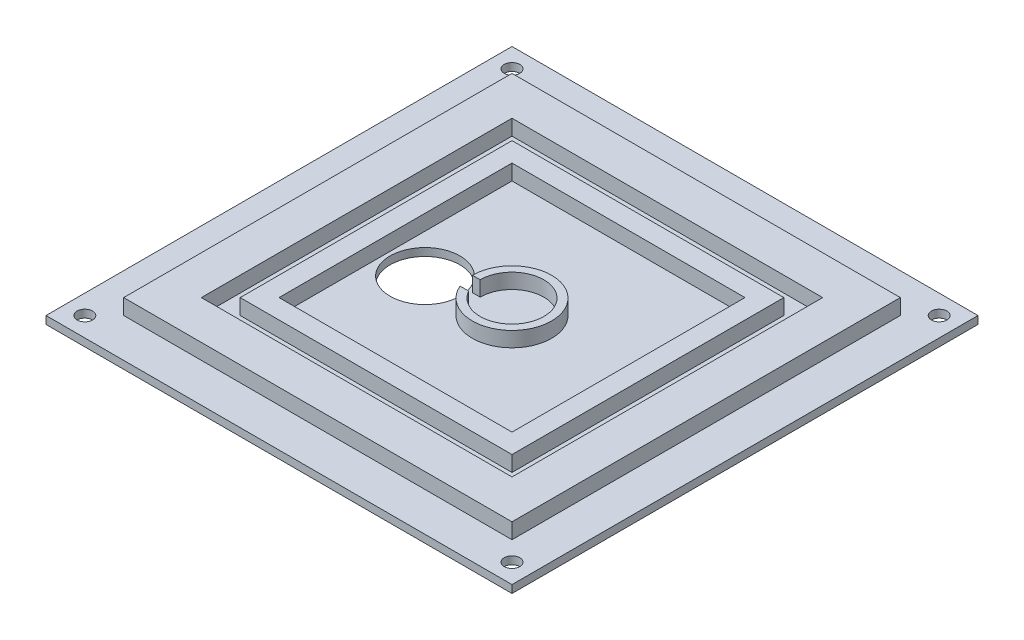
SolidWorks part; units mm, degrees
ref_plane "Front Plane" through (0, 0, 0) normal (0, 0, 1) x (1, 0, 0)
ref_plane "Top Plane" through (0, 0, 0) normal (0, 1, 0) x (1, 0, 0)
ref_plane "Right Plane" through (0, 0, 0) normal (1, 0, 0) x (0, 0, -1)
sketch "Sketch1" plane through (0, 0, 0) normal (0, 1, 0) x (1, 0, 0)
  line L1 (-76.2, 76.2) -> (76.2, 76.2)
  line L2 (-76.2, 76.2) -> (-76.2, -76.2)
  line L3 (-76.2, -76.2) -> (76.2, -76.2)
  line L4 (76.2, 76.2) -> (76.2, -76.2)
  line L5 (-76.2, 76.2) -> (76.2, -76.2) construction
  line L6 (-76.2, -76.2) -> (76.2, 76.2) construction
  point P0 (0, 0)
  dimension "D1" = 152.4
  dimension "D2" = 152.4
extrude "Boss-Extrude1" add sketch "Sketch1" against normal blind 2.54
sketch "Sketch2" plane through (0, 0, 0) normal (0, 1, 0) x (1, 0, 0)
  line L1 (63.5, -63.5) -> (-63.5, -63.5)
  line L2 (63.5, -63.5) -> (63.5, 63.5)
  line L3 (63.5, 63.5) -> (-63.5, 63.5)
  line L4 (-63.5, -63.5) -> (-63.5, 63.5)
  line L5 (63.5, -63.5) -> (-63.5, 63.5) construction
  line L6 (63.5, 63.5) -> (-63.5, -63.5) construction
  line L7 (-57.15, 57.15) -> (57.15, 57.15)
  line L8 (-57.15, 57.15) -> (-57.15, -57.15)
  line L9 (-57.15, -57.15) -> (57.15, -57.15)
  line L10 (57.15, 57.15) -> (57.15, -57.15)
  line L11 (-57.15, 57.15) -> (57.15, -57.15) construction
  line L12 (-57.15, -57.15) -> (57.15, 57.15) construction
  point P0 (0, 0)
  point P6 (0, 0)
  dimension "D1" = 127
  dimension "D2" = 127
  dimension "D3" = 114.3
  dimension "D4" = 114.3
extrude "Boss-Extrude3" add sketch "Sketch2" along normal blind 5.08 contours L2 L1 L4 L3
sketch "Sketch3" plane through (0, 5.08, 0) normal (0, 1, 0) x (1, 0, 0)
  line L1 (-50.8, 50.8) -> (50.8, 50.8)
  line L2 (-50.8, 50.8) -> (-50.8, -50.8)
  line L3 (-50.8, -50.8) -> (50.8, -50.8)
  line L4 (50.8, 50.8) -> (50.8, -50.8)
  line L5 (-50.8, 50.8) -> (50.8, -50.8) construction
  line L6 (-50.8, -50.8) -> (50.8, 50.8) construction
  point P0 (0, 0)
  dimension "D1" = 101.6
  dimension "D2" = 101.6
extrude "Cut-Extrude2" cut sketch "Sketch3" against normal blind 5.08
sketch "Sketch5" plane through (0, 0, 0) normal (0, 1, 0) x (1, 0, 0)
  line L1 (-44.45, 44.45) -> (44.45, 44.45)
  line L2 (-44.45, 44.45) -> (-44.45, -44.45)
  line L3 (-44.45, -44.45) -> (44.45, -44.45)
  line L4 (44.45, 44.45) -> (44.45, -44.45)
  line L5 (-44.45, 44.45) -> (44.45, -44.45) construction
  line L6 (-44.45, -44.45) -> (44.45, 44.45) construction
  point P0 (0, 0)
  dimension "D1" = 88.9
  dimension "D2" = 88.9
extrude "Boss-Extrude4" add sketch "Sketch5" along normal blind 5.08
sketch "Sketch6" plane through (0, 5.08, 0) normal (0, 1, 0) x (1, 0, 0)
  line L1 (-38.1, 38.1) -> (38.1, 38.1)
  line L2 (-38.1, 38.1) -> (-38.1, -38.1)
  line L3 (-38.1, -38.1) -> (38.1, -38.1)
  line L4 (38.1, 38.1) -> (38.1, -38.1)
  line L5 (-38.1, 38.1) -> (38.1, -38.1) construction
  line L6 (-38.1, -38.1) -> (38.1, 38.1) construction
  point P0 (0, 0)
  dimension "D1" = 76.2
  dimension "D2" = 76.2
extrude "Cut-Extrude3" cut sketch "Sketch6" against normal blind 5.08
sketch "Sketch7" plane through (0, 0, 0) normal (0, 1, 0) x (1, 0, 0)
  line L0 (-10.414, 0) -> (-12.954, 0)
  line L1 (-9.0909, -5.08) -> (-11.9164, -5.08)
  line L2 (-38.1, -38.1) -> (38.1, -38.1) construction
  arc A0 (-11.9164, -5.08) -> (-12.954, 0) centre (0, 0) ccw
  arc A1 (-9.0909, -5.08) -> (-10.414, 0) centre (0, 0) ccw
  dimension "D1" = 12.954
  dimension "D2" = 10.414
  dimension "D3" = 5.08
  dimension "D4" = 33.02
extrude "Boss-Extrude5" add sketch "Sketch7" along normal blind 2.794
sketch "Sketch8" plane through (0, 0, 0) normal (0, 1, 0) x (1, 0, 0)
  line L0 (-38.1, -38.1) -> (38.1, -38.1) construction
  circle A1 centre (-25.4, -3.048) radius 11.43
  dimension "D2" = 22.86
  dimension "D3" = 25.4
  dimension "D4" = 35.052
extrude "Cut-Extrude4" cut sketch "Sketch8" against normal through all contours A1
sketch "Sketch9" plane through (0, 0, 0) normal (0, 1, 0) x (1, 0, 0)
  line L0 (-76.2, -76.2) -> (76.2, -76.2) construction
  line L1 (-76.2, 76.2) -> (-76.2, -76.2) construction
  line L2 (76.2, -76.2) -> (76.2, 76.2) construction
  line L3 (76.2, 76.2) -> (-76.2, 76.2) construction
  circle A0 centre (-69.85, -69.85) radius 2.54
  circle A1 centre (69.85, -69.85) radius 2.54
  circle A2 centre (69.85, 69.85) radius 2.54
  circle A3 centre (-69.85, 69.85) radius 2.54
  dimension "D3" = 5.08
  dimension "D4" = 5.08
  dimension "D6" = 5.08
  dimension "D7" = 5.08
  dimension "D1" = 6.35
  dimension "D2" = 6.35
  dimension "D5" = 6.35
  dimension "D8" = 6.35
  dimension "D9" = 6.35
  dimension "D10" = 6.35
  dimension "D11" = 6.35
  dimension "D12" = 6.35
extrude "Cut-Extrude5" cut sketch "Sketch9" against normal through all
extrude "Boss-Extrude6" add sketch "Sketch7<2>" along normal blind 4.9276
sketch "Sketch7<2>" plane through (0, 0, 0) normal (0, 1, 0) x (1, 0, 0) same geometry as "Sketch7"
